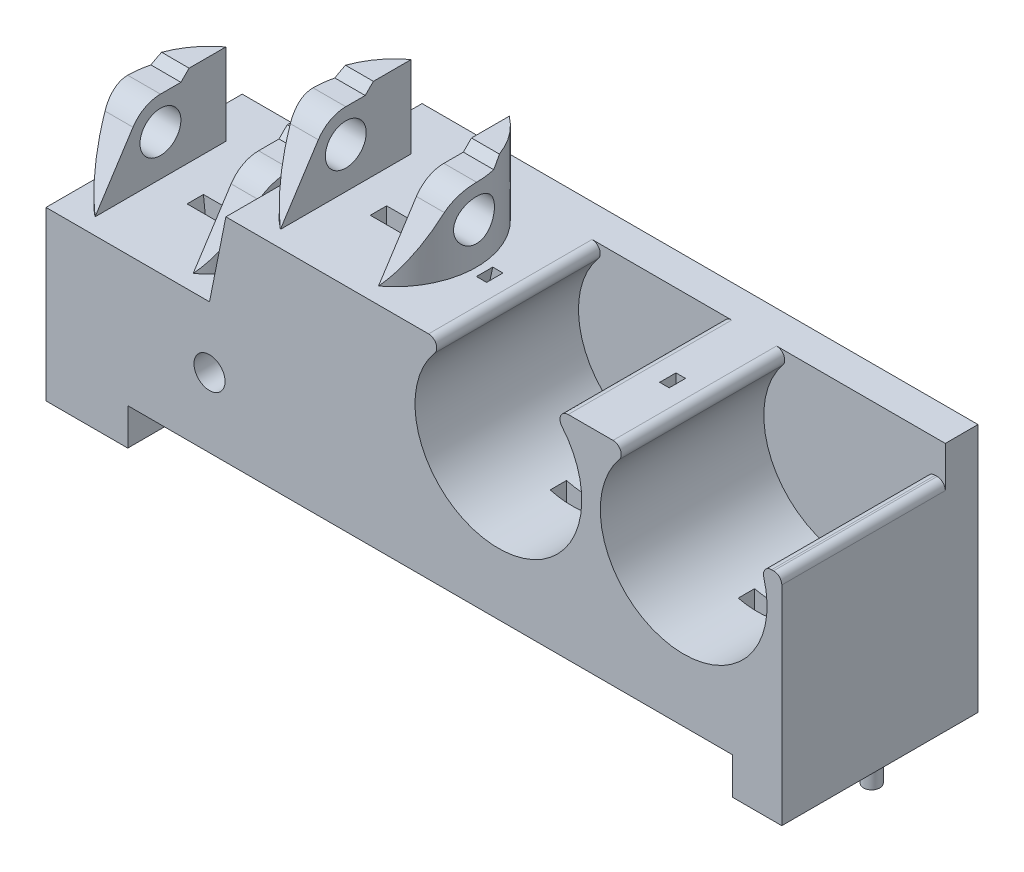
SolidWorks part; units mm, degrees
ref_plane "Front Plane" through (0, 0, 0) normal (0, 0, 1) x (1, 0, 0)
ref_plane "Top Plane" through (0, 0, 0) normal (0, 1, 0) x (1, 0, 0)
ref_plane "Right Plane" through (0, 0, 0) normal (1, 0, 0) x (0, 0, -1)
sketch "Sketch2" plane through (0, 0, 0) normal (0, 0, 1) x (1, 0, 0)
  line L1 (0, 0) -> (114.3, 0)
  line L2 (0, 0) -> (0, 142.875)
  line L3 (0, 142.875) -> (114.3, 142.875)
  line L4 (114.3, 0) -> (114.3, 142.875)
  dimension "D1" = 114.3
  dimension "D2" = 142.875
extrude "Boss-Extrude2" add sketch "Sketch2" along normal blind 30.48 contours L3 L4 L1 L2
fillet "Fillet1" radius 71.501 1 edges at (0, 0, 15.24) second distance 25.4 first distance on face at (0, 71.4375, 15.24)
sketch "Sketch3" plane through (0, 142.875, 0) normal (0, 1, 0) x (1, 0, 0)
  line L0 (0, -30.48) -> (114.3, -30.48) construction
  line L1 (33.8666, -7.62) -> (33.8666, -27.94)
  line L10 (0, -30.48) -> (0, 0) construction
  line L13 (49.1066, -7.62) -> (49.1066, -27.94)
  arc A8 (33.8666, -7.62) -> (33.8666, -27.94) centre (41.4866, -17.78) ccw
  arc A9 (49.1066, -27.94) -> (49.1066, -7.62) centre (41.4866, -17.78) ccw
  dimension "D1" = 25.4
  dimension "D2" = 12.7
  dimension "D3" = 41.4866
  dimension "D5" = 7.62
  dimension "D6" = 7.62
extrude "Boss-Extrude3" add sketch "Sketch3" along normal blind 11.43
sketch "Sketch5" plane through (0, 0, 30.48) normal (0, 0, 1) x (1, 0, 0)
  line L0 (62.6533, 142.875) -> (77.8933, 142.875)
  line L1 (0, 142.875) -> (114.3, 142.875) construction
  line L2 (0, 71.501) -> (0, 142.875) construction
  line L3 (114.3, 0) -> (114.3, 142.875) construction
  line L4 (91.44, 143.0325) -> (106.68, 143.0325)
  arc A0 (62.6533, 142.875) -> (77.8933, 142.875) centre (70.2733, 132.3992) ccw
  arc A1 (91.44, 143.0325) -> (106.68, 143.0325) centre (99.06, 132.5567) ccw
  dimension "D1" = 25.908
  dimension "D5" = 25.908
  dimension "D2" = 15.24
  dimension "D3" = 0
  dimension "D4" = 70.2733
  dimension "D6" = 15.24
  dimension "D7" = 15.24
extrude "Cut-Extrude2" cut sketch "Sketch5" against normal blind 25.4
fillet "Fillet2" radius 1.27 3 edges at (91.2281, 142.875, 17.78) (77.8933, 142.875, 17.78) (62.6533, 142.875, 17.78)
sketch "Sketch7" plane through (0, 142.875, 0) normal (0, 1, 0) x (1, 0, 0)
  line L0 (0, -30.48) -> (59.4301, -30.48) construction
  line L1 (0, 0) -> (27.94, 0)
  line L2 (0, 0) -> (0, -30.48)
  line L3 (0, -30.48) -> (27.94, -30.48)
  line L4 (27.94, 0) -> (27.94, -30.48)
  dimension "D1" = 27.94
extrude "Cut-Extrude4" cut sketch "Sketch7" against normal blind 12.7
sketch "Sketch8" plane through (0, 130.175, 0) normal (0, 1, 0) x (1, 0, 0)
  line L6 (0, -30.48) -> (27.94, -30.48) construction
  line L7 (0, 0) -> (0, -30.48) construction
  line L8 (5.08, -7.62) -> (5.08, -27.94)
  line L9 (20.32, -7.62) -> (20.32, -27.94)
  arc A4 (5.08, -7.62) -> (5.08, -27.94) centre (12.7, -17.78) ccw
  arc A5 (20.32, -27.94) -> (20.32, -7.62) centre (12.7, -17.78) ccw
  dimension "D1" = 25.4
  dimension "D2" = 12.7
  dimension "D3" = 12.7
  dimension "D4" = 7.62
  dimension "D5" = 7.62
extrude "Boss-Extrude4" add sketch "Sketch8" along normal blind 11.43
sketch "Sketch10" plane through (0, 0, 30.48) normal (0, 0, 1) x (1, 0, 0)
  line L0 (114.3, 0) -> (114.3, 142.875) construction
  line L1 (63.5, 109.855) -> (12.7, 109.855)
  line L3 (63.5, 12.7) -> (38.1, 12.7)
  line L4 (12.7, 109.855) -> (12.7, 61.2775)
  line L5 (0, 71.501) -> (0, 130.175) construction
  line L6 (25.4, 0) -> (114.3, 0) construction
  line L7 (27.94, 142.875) -> (59.4301, 142.875) construction
  line L8 (12.7, 61.2775) -> (38.1, 12.7)
  line L14 (63.5, 94.615) -> (63.5, 12.7)
  line L15 (63.5, 109.855) -> (106.68, 109.855)
  line L17 (63.5, 94.615) -> (106.68, 94.615)
  line L18 (106.68, 109.855) -> (106.68, 94.615)
  dimension "D1" = 7.62
  dimension "D2" = 12.7
  dimension "D3" = 12.7
  dimension "D4" = 33.02
  dimension "D5" = 15.24
extrude "Cut-Extrude6" cut sketch "Sketch10" against normal blind 25.4
sketch "Sketch11" plane through (49.1066, 0, 0) normal (-1, 0, 0) x (0, 0, 1)
  line L0 (7.62, 154.305) -> (27.94, 154.305) construction
  line L1 (27.94, 154.305) -> (27.94, 142.875) construction
  line L2 (27.94, 154.305) -> (7.62, 154.305) construction
  line L3 (22.0449, 151.9849) -> (27.94, 142.875)
  line L4 (27.94, 142.875) -> (27.94, 154.305)
  line L5 (27.94, 154.305) -> (17.78, 154.305)
  circle A0 centre (17.78, 149.225) radius 3.175
  arc A1 (17.78, 154.305) -> (22.0449, 151.9849) centre (17.78, 149.225) cw
  dimension "D2" = 6.35
  dimension "D1" = 5.08
  dimension "D3" = 10.16
extrude "Cut-Extrude7" cut sketch "Sketch11" against normal through all both and the other way through all
sketch "Sketch12" plane through (20.32, 0, 0) normal (-1, 0, 0) x (0, 0, 1)
  line L0 (27.94, 141.605) -> (27.94, 130.175) construction
  line L1 (7.62, 141.605) -> (27.94, 141.605) construction
  line L2 (27.94, 141.605) -> (7.62, 141.605) construction
  line L3 (22.0449, 139.2849) -> (27.94, 130.175)
  line L4 (27.94, 130.175) -> (27.94, 141.605)
  line L5 (27.94, 141.605) -> (17.78, 141.605)
  circle A0 centre (17.78, 136.525) radius 3.175
  arc A1 (17.78, 141.605) -> (22.0449, 139.2849) centre (17.78, 136.525) cw
  dimension "D1" = 6.35
  dimension "D2" = 10.16
  dimension "D3" = 5.08
extrude "Cut-Extrude8" cut sketch "Sketch12" against normal up to surface (7.62 mm away) and the other way through all up to face at (27.94, 136.525, 15.24)
chamfer "Chamfer1" distance 12.7 distance2 2.54 1 edges at (27.94, 130.175, 15.24) first distance on face at (27.94, 136.525, 15.24)
sketch "Sketch13" plane through (0, 0, 30.48) normal (0, 0, 1) x (1, 0, 0)
  line L1 (114.3, 142.875) -> (106.68, 142.875)
  line L2 (114.3, 142.875) -> (114.3, 137.795)
  line L3 (114.3, 137.795) -> (106.68, 137.795)
  line L4 (106.68, 142.875) -> (106.68, 137.795)
  dimension "D1" = 7.62
  dimension "D2" = 5.08
extrude "Cut-Extrude9" cut sketch "Sketch13" against normal up to surface (25.4 mm away) up to face at (95.7606, 134.9038, 5.08)
fillet "Fillet4" radius 1.27 2 edges at (114.3, 137.795, 17.78) (110.9076, 137.795, 17.78)
sketch "Sketch14" plane through (0, 0, 30.48) normal (0, 0, 1) x (1, 0, 0)
  line L0 (114.3, 0) -> (114.3, 136.525) construction
  line L1 (114.3, 12.7) -> (81.28, 12.7)
  line L2 (114.3, 12.7) -> (114.3, 83.82)
  line L3 (114.3, 83.82) -> (81.28, 83.82)
  line L4 (81.28, 12.7) -> (81.28, 26.67)
  line L5 (25.4, 0) -> (114.3, 0) construction
  line L6 (81.28, 69.85) -> (81.28, 83.82)
  line L7 (81.28, 69.85) -> (111.76, 69.85)
  line L9 (81.28, 26.67) -> (111.76, 26.67)
  line L10 (111.76, 69.85) -> (111.76, 26.67)
  dimension "D1" = 12.7
  dimension "D2" = 71.12
  dimension "D3" = 33.02
  dimension "D4" = 13.97
  dimension "D5" = 13.97
  dimension "D6" = 30.48
extrude "Cut-Extrude10" cut sketch "Sketch14" against normal through all
chamfer "Chamfer2" distance 12.7 distance2 12.7 2 edges at (81.28, 19.685, 30.48) (81.28, 76.835, 30.48)
sketch "Sketch15" plane through (0, 0, 0) normal (0, -1, 0) x (1, 0, 0)
  line L0 (114.3, 30.48) -> (114.3, 0) construction
  line L1 (25.4, 30.48) -> (114.3, 30.48) construction
  circle A0 centre (99.06, 17.78) radius 3.175
  dimension "D1" = 6.35
  dimension "D2" = 15.24
  dimension "D3" = 12.7
extrude "Cut-Extrude11" cut sketch "Sketch15" against normal up to surface (109.855 mm away) up to face at (59.69, 109.855, 17.78)
sketch "Sketch16" plane through (0, 141.605, 0) normal (0, 1, 0) x (1, 0, 0)
  line L0 (0.407, -14.5906) -> (5.08, -14.605)
  line L1 (5.08, -14.605) -> (5.08, -7.62)
  line L2 (20.32, -14.605) -> (24.9967, -14.605)
  line L3 (20.32, -7.62) -> (20.32, -17.78) construction
  line L4 (20.32, -7.62) -> (20.32, -14.605)
  arc A0 (24.9967, -14.605) -> (20.32, -7.62) centre (12.7, -17.78) ccw
  arc A1 (5.08, -7.62) -> (0.407, -14.5906) centre (12.7, -17.78) ccw
extrude "Boss-Extrude5" add sketch "Sketch16" along normal blind 1.27
chamfer "Chamfer3" distance 1.27 angle 45 2 edges at (22.6584, 142.875, 14.605) (2.7435, 142.875, 14.5978)
sketch "Sketch17" plane through (0, 154.305, 0) normal (0, 1, 0) x (1, 0, 0)
  line L0 (29.1505, -14.7614) -> (33.8666, -14.7614)
  line L1 (33.8666, -17.78) -> (33.8666, -7.62) construction
  line L2 (33.8666, -14.7614) -> (33.8666, -7.62)
  line L4 (49.1066, -14.7614) -> (53.8226, -14.7614)
  line L5 (49.1066, -7.62) -> (49.1066, -17.78) construction
  line L6 (49.1066, -7.62) -> (49.1066, -14.7614)
  arc A0 (33.8666, -7.62) -> (29.1505, -14.7614) centre (41.4866, -17.78) ccw
  arc A1 (53.8226, -14.7614) -> (49.1066, -7.62) centre (41.4866, -17.78) ccw
extrude "Boss-Extrude6" add sketch "Sketch17" along normal blind 1.27
chamfer "Chamfer4" distance 1.27 angle 45 2 edges at (51.4646, 155.575, 14.7614) (31.5086, 155.575, 14.7614)
fillet "Fillet5" radius 15.24 1 edges at (111.76, 48.26, 30.48)
sketch "Sketch19" plane through (0, 0, 30.48) normal (0, 0, 1) x (1, 0, 0)
  line L0 (111.76, 69.85) -> (111.76, 26.67) construction
  line L1 (81.28, 52.07) -> (111.76, 52.07)
  line L3 (81.28, 57.15) -> (111.76, 57.15)
  line L4 (111.76, 52.07) -> (111.76, 57.15)
  line L5 (81.28, 52.07) -> (111.76, 57.15) construction
  line L6 (81.28, 57.15) -> (111.76, 52.07) construction
  line L7 (68.58, 69.85) -> (96.52, 69.85) construction
  line L9 (81.28, 57.15) -> (69.85, 57.15)
  line L11 (81.28, 52.07) -> (69.85, 52.07)
  line L12 (69.85, 57.15) -> (69.85, 52.07)
  point P0 (96.52, 54.61)
  dimension "D1" = 15.24
  dimension "D2" = 5.08
  dimension "D3" = 12.7
  dimension "D4" = 11.43
extrude "Cut-Extrude12" cut sketch "Sketch19" against normal blind 16.51
sketch "Sketch20" plane through (63.5, 0, 0) normal (-1, 0, 0) x (0, 0, 1)
  line L0 (30.48, 12.7) -> (30.48, 94.615) construction
  line L1 (17.78, 40.64) -> (20.32, 40.64)
  line L2 (17.78, 40.64) -> (17.78, 38.1)
  line L3 (17.78, 38.1) -> (20.32, 38.1)
  line L4 (20.32, 40.64) -> (20.32, 38.1)
  line L5 (5.08, 12.7) -> (30.48, 12.7) construction
  dimension "D1" = 2.54
  dimension "D2" = 2.54
  dimension "D3" = 12.7
  dimension "D4" = 25.4
extrude "Cut-Extrude13" cut sketch "Sketch20" against normal through all
fillet "Fillet6" radius 1.27 1 edges at (63.5, 38.1, 19.05)
ref_plane "Plane1" through (0, 0, 17.78) normal (0, 0, 1) x (1, 0, 0)
sketch "Sketch21" plane through (0, 0, 17.78) normal (0, 0, 1) x (1, 0, 0)
  line L0 (12.7, 109.855) -> (10.4859, 130.175)
  line L1 (0, 130.175) -> (25.4, 130.175) construction
  line L2 (10.4859, 130.175) -> (15.5659, 130.175)
  line L3 (15.5659, 130.175) -> (17.78, 109.855)
  line L4 (106.68, 109.855) -> (12.7, 109.855) construction
  line L5 (17.78, 109.855) -> (12.7, 109.855)
  line L6 (55.4297, 142.875) -> (50.8604, 121.6537)
  line L7 (27.94, 142.875) -> (59.4301, 142.875) construction
  line L8 (38.9466, 142.875) -> (44.0266, 142.875)
  line L9 (38.9466, 142.875) -> (38.9466, 109.855)
  line L10 (38.9466, 109.855) -> (44.0266, 109.855)
  line L11 (44.0266, 142.875) -> (44.0266, 109.855)
  line L12 (33.8666, 151.9849) -> (33.8666, 142.875) construction
  line L13 (50.8604, 121.6537) -> (50.8604, 109.855)
  line L14 (66.8866, 119.8958) -> (71.9666, 119.8958)
  line L15 (66.8866, 119.8958) -> (66.8866, 109.855)
  line L16 (66.8866, 109.855) -> (71.9666, 109.855)
  line L17 (71.9666, 119.8958) -> (71.9666, 109.855)
  line L18 (96.0966, 119.9462) -> (101.1766, 119.9462)
  line L19 (96.0966, 119.9462) -> (96.0966, 109.855)
  line L20 (96.0966, 109.855) -> (101.1766, 109.855)
  line L21 (101.1766, 119.9462) -> (101.1766, 109.855)
  line L22 (50.8604, 109.855) -> (52.4497, 109.855)
  line L23 (52.4497, 109.855) -> (52.4497, 121.6537)
  line L24 (52.4497, 121.6537) -> (57.0191, 142.875)
  line L25 (57.0191, 142.875) -> (55.4297, 142.875)
  line L36 (106.68, 94.615) -> (106.68, 109.855) construction
  line L37 (106.68, 103.1464) -> (114.3, 103.1464)
  line L38 (106.68, 103.1464) -> (106.68, 101.7444)
  line L39 (106.68, 101.7444) -> (114.3, 101.7444)
  line L40 (114.3, 103.1464) -> (114.3, 101.7444)
  line L41 (114.3, 83.82) -> (114.3, 136.525) construction
  line L42 (81.1166, 142.875) -> (88.085, 142.875) construction
  line L43 (83.8937, 142.875) -> (85.379, 142.875)
  line L44 (83.8937, 142.875) -> (83.8937, 109.855)
  line L45 (83.8937, 109.855) -> (85.379, 109.855)
  line L46 (85.379, 142.875) -> (85.379, 109.855)
  arc A0 (60.3982, 140.7831) -> (80.1484, 140.7831) centre (70.2733, 132.3992) ccw construction
  arc A1 (89.0649, 140.7971) -> (111.4997, 136.1707) centre (99.06, 132.5567) ccw construction
  point P9 (13.0259, 130.175)
  dimension "D1" = 5.08
  dimension "D2" = 2.5251
  dimension "D3" = 5.08
  dimension "D4" = 5.08
  dimension "D5" = 5.08
  dimension "D6" = 22.86
  dimension "D7" = 5.08
  dimension "D8" = 24.13
extrude "Cut-Extrude14" cut sketch "Sketch21" against normal blind 1.27 and the other way blind 1.27
fillet "Fillet7" radius 11.43 1 edges at (63.5, 94.615, 17.78)
sketch "Sketch22" plane through (0, 12.7, 0) normal (0, 1, 0) x (1, 0, 0)
  line L0 (38.1, -5.08) -> (38.1, -30.48) construction
  circle A0 centre (43.18, -11.9083) radius 1.27
  circle A1 centre (48.26, -11.9083) radius 1.27
  circle A2 centre (53.34, -11.9083) radius 1.27
  circle A3 centre (58.42, -11.9083) radius 1.27
  circle A4 centre (43.18, -22.0683) radius 1.27
  circle A5 centre (48.26, -22.0683) radius 1.27
  circle A6 centre (53.34, -22.0683) radius 1.27
  circle A7 centre (58.42, -22.0683) radius 1.27
  dimension "D1" = 2.54
  dimension "D2" = 2.54
  dimension "D3" = 2.54
  dimension "D4" = 2.54
  dimension "D5" = 2.54
  dimension "D6" = 2.54
  dimension "D7" = 2.54
  dimension "D8" = 2.54
  dimension "D9" = 10.16
  dimension "D10" = 10.16
  dimension "D11" = 10.16
  dimension "D12" = 10.16
  dimension "D13" = 5.08
  dimension "D14" = 5.08
  dimension "D15" = 5.08
  dimension "D16" = 5.08
extrude "Cut-Extrude15" cut sketch "Sketch22" against normal up to surface (12.7 mm away) up to face at (99.06, 0, 14.605)
sketch "Sketch23" plane through (0, 0, 0) normal (0, 0, -1) x (-1, 0, 0)
  line L0 (0, 71.501) -> (0, 130.175) construction
  line L1 (-25.4, 0) -> (-114.3, 0) construction
  circle A0 centre (-25.4, 120.65) radius 2.413
  circle A1 centre (-19.05, 25.4) radius 2.413
  circle A2 centre (-82.55, 6.35) radius 2.413
  dimension "D1" = 4.826
  dimension "D4" = 4.826
  dimension "D9" = 4.826
  dimension "D2" = 25.4
  dimension "D3" = 120.65
  dimension "D5" = 19.05
  dimension "D6" = 25.4
  dimension "D7" = 6.35
  dimension "D8" = 82.55
extrude "Cut-Extrude16" cut sketch "Sketch23" against normal through all both and the other way through all
sketch "Sketch24" plane through (0, 0, 0) normal (0, -1, 0) x (1, 0, 0)
  line L0 (25.4, 0) -> (114.3, 0) construction
  line L1 (25.4, 30.48) -> (38.1, 30.48)
  line L2 (25.4, 30.48) -> (25.4, 0)
  line L3 (25.4, 0) -> (38.1, 0)
  line L4 (38.1, 30.48) -> (38.1, 0)
  line L5 (25.4, 30.48) -> (114.3, 30.48) construction
  line L6 (66.3452, 30.48) -> (79.0452, 30.48)
  line L7 (66.3452, 30.48) -> (66.3452, 0)
  line L8 (66.3452, 0) -> (79.0452, 0)
  line L9 (79.0452, 30.48) -> (79.0452, 0)
  dimension "D1" = 12.7
  dimension "D2" = 12.7
extrude "Boss-Extrude7" add sketch "Sketch24" along normal blind 25.4
sketch "Sketch25" plane through (79.0452, 0, 0) normal (1, 0, 0) x (0, 0, -1)
  line L0 (-30.48, -25.4) -> (0, -25.4) construction
  line L1 (0, -25.4) -> (0, 0) construction
  circle A0 centre (-15.24, -12.7) radius 2.54
  dimension "D3" = 5.08
  dimension "D1" = 12.7
  dimension "D2" = 15.24
extrude "Cut-Extrude17" cut sketch "Sketch25" against normal through all
sketch "Sketch27" plane through (0, 0, 0) normal (0, 1, 0) x (1, 0, 0)
  line L1 (-3.0962, 64.4361) -> (140.3617, 64.4361)
  line L2 (-3.0962, 64.4361) -> (-3.0962, -35.74)
  line L3 (-3.0962, -35.74) -> (140.3617, -35.74)
  line L4 (140.3617, 64.4361) -> (140.3617, -35.74)
extrude "Cut-Extrude18" cut sketch "Sketch27" against normal blind 43.18 and the other way blind 104.14
sketch "Sketch28" plane through (0, 104.14, 0) normal (0, -1, 0) x (1, 0, 0)
  line L0 (106.68, 30.48) -> (114.3, 30.48) construction
  line L1 (114.3, 30.48) -> (114.3, 0) construction
  line L2 (0, 30.48) -> (12.7, 30.48) construction
  line L4 (0, 30.48) -> (0, 0) construction
  circle A0 centre (6.35, 12.7) radius 1.27
  circle A1 centre (110.49, 12.7) radius 1.27
  point P10 (0, 0)
  point P12 (0, 12.2771)
  dimension "D1" = 2.54
  dimension "D2" = 2.54
  dimension "D3" = 17.78
  dimension "D4" = 3.81
  dimension "D5" = 17.78
  dimension "D6" = 6.35
extrude "Boss-Extrude8" add sketch "Sketch28" along normal blind 5.08
